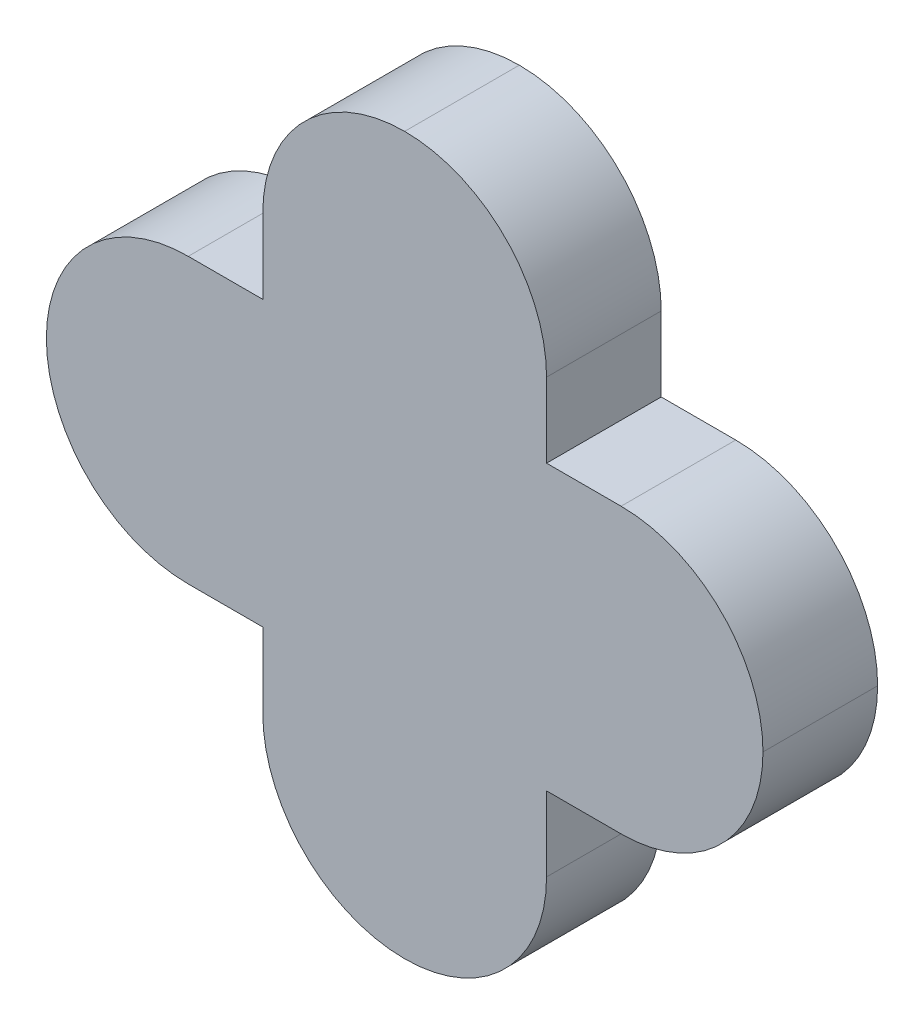
SolidWorks part; units mm, degrees
ref_plane "Front Plane" through (0, 0, 0) normal (0, 0, 1) x (1, 0, 0)
ref_plane "Top Plane" through (0, 0, 0) normal (0, 1, 0) x (1, 0, 0)
ref_plane "Right Plane" through (0, 0, 0) normal (1, 0, 0) x (0, 0, -1)
sketch "Sketch1" plane through (0, 0, 0) normal (0, 0, 1) x (1, 0, 0)
  line L0 (-2.475, 6.25) -> (-6.25, 6.25)
  line L1 (-6.25, -6.25) -> (6.25, -6.25)
  line L2 (-6.25, -6.25) -> (-6.25, 6.25)
  line L3 (-6.25, 6.25) -> (6.25, 6.25)
  line L4 (6.25, -6.25) -> (6.25, 6.25)
  line L5 (-6.25, -6.25) -> (6.25, 6.25) construction
  line L6 (-6.25, 6.25) -> (6.25, -6.25) construction
  line L7 (0, 6.25) -> (0, -6.25) construction
  line L8 (-2.475, 6.25) -> (-6.25, 6.25)
  line L9 (-2.475, 6.25) -> (-2.475, 2.475)
  line L10 (-2.475, 2.475) -> (-6.25, 2.475)
  line L11 (-6.25, 6.25) -> (-6.25, 2.475)
  line L12 (2.475, 2.475) -> (6.25, 2.475)
  line L13 (6.25, 6.25) -> (6.25, 2.475)
  line L14 (2.475, 6.25) -> (6.25, 6.25)
  line L15 (2.475, 6.25) -> (2.475, 2.475)
  line L16 (-6.25, 0) -> (6.25, 0) construction
  line L17 (-2.475, -2.475) -> (-6.25, -2.475)
  line L18 (-6.25, -6.25) -> (-6.25, -2.475)
  line L19 (-2.475, -6.25) -> (-6.25, -6.25)
  line L20 (-2.475, -6.25) -> (-2.475, -2.475)
  line L21 (6.25, -6.25) -> (6.25, -2.475)
  line L22 (2.475, -2.475) -> (6.25, -2.475)
  line L23 (2.475, -6.25) -> (2.475, -2.475)
  line L24 (2.475, -6.25) -> (6.25, -6.25)
  point P0 (0, 0)
  dimension "D1" = 12.5
  dimension "D2" = 12.5
  dimension "D3" = 3.775
  dimension "D4" = 3.775
extrude "Boss-Extrude1" add sketch "Sketch1" along normal blind 2 contours L1 L23 L22 L4 L12 L15 L3 L9 L10 L2 L17 L20 region at (0, 0, 0)
fillet "Fillet1" radius 2.475 8 edges at (2.475, 6.25, 1) (6.25, 2.475, 1) (6.25, -2.475, 1) (2.475, -6.25, 1) (-2.475, -6.25, 1) (-6.25, -2.475, 1) (-6.25, 2.475, 1) (-2.475, 6.25, 1)
